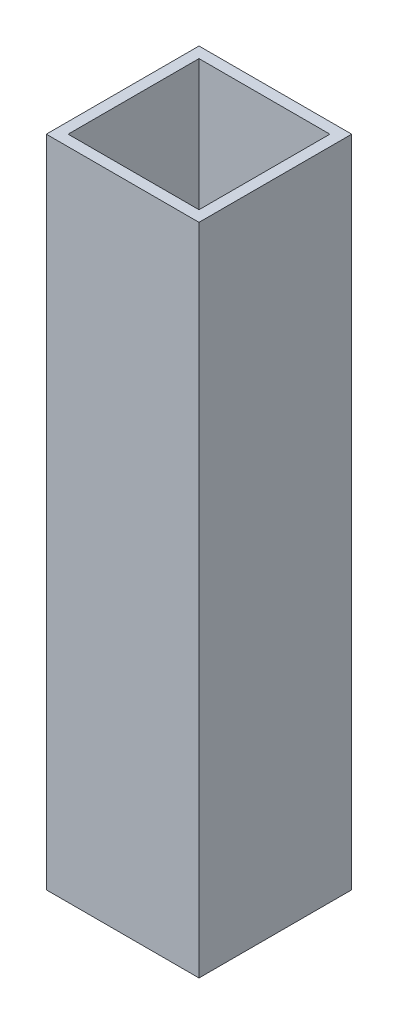
SolidWorks part; units mm, degrees
material "6061-T6 (SS)"
ref_plane "Front Plane" through (0, 0, 0) normal (0, 0, 1) x (1, 0, 0)
ref_plane "Top Plane" through (0, 0, 0) normal (0, 1, 0) x (1, 0, 0)
ref_plane "Right Plane" through (0, 0, 0) normal (1, 0, 0) x (0, 0, -1)
sketch "Sketch1" plane through (0, 0, 0) normal (0, 1, 0) x (1, 0, 0)
  line L1 (-22.225, -22.225) -> (22.225, -22.225)
  line L2 (-22.225, -22.225) -> (-22.225, 22.225)
  line L3 (-22.225, 22.225) -> (22.225, 22.225)
  line L4 (22.225, -22.225) -> (22.225, 22.225)
  line L5 (-22.225, -22.225) -> (22.225, 22.225) construction
  line L6 (-22.225, 22.225) -> (22.225, -22.225) construction
  line L7 (-19.05, -19.05) -> (19.05, -19.05)
  line L8 (-19.05, -19.05) -> (-19.05, 19.05)
  line L9 (-19.05, 19.05) -> (19.05, 19.05)
  line L10 (19.05, -19.05) -> (19.05, 19.05)
  line L11 (-19.05, -19.05) -> (19.05, 19.05) construction
  line L12 (-19.05, 19.05) -> (19.05, -19.05) construction
  point P0 (0, 0)
  point P6 (0, 0)
  dimension "D1" = 44.45
  dimension "D2" = 3.175
extrude "Boss-Extrude1" add sketch "Sketch1" along normal blind 95.25 and the other way blind 95.25
